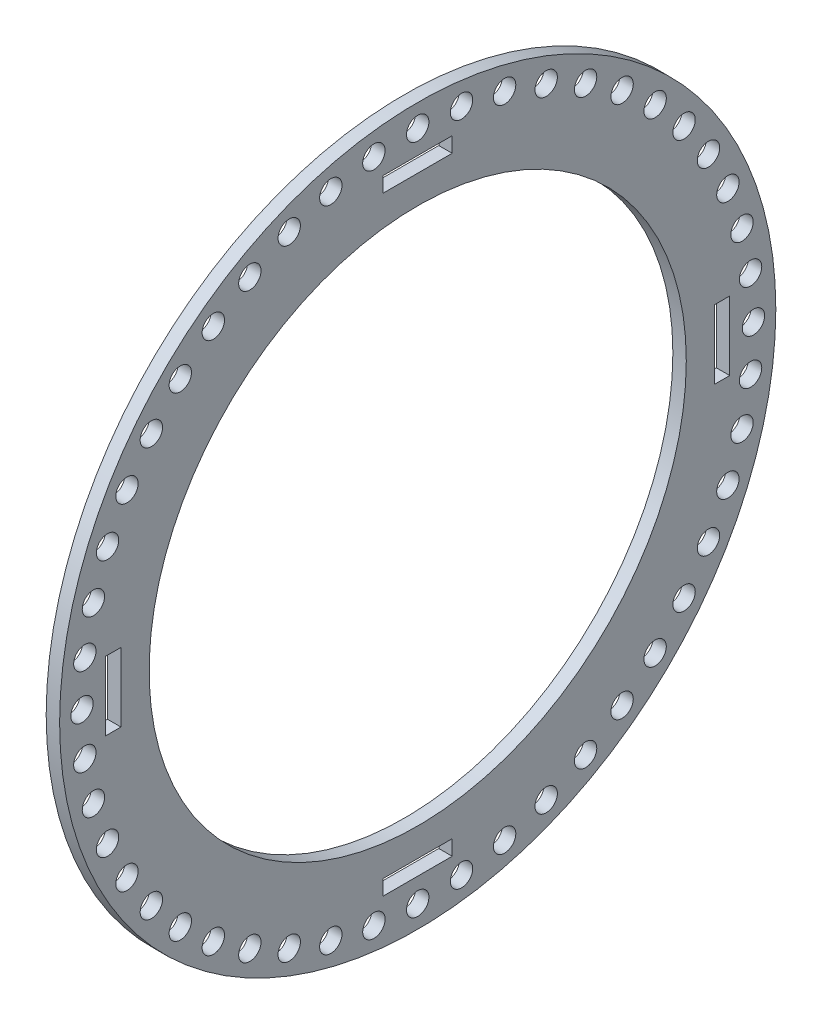
SolidWorks part; units mm, degrees
material "AISI 304"
ref_plane "Front Plane" through (0, 0, 0) normal (0, 0, 1) x (1, 0, 0)
ref_plane "Top Plane" through (0, 0, 0) normal (0, 1, 0) x (1, 0, 0)
ref_plane "Right Plane" through (0, 0, 0) normal (1, 0, 0) x (0, 0, -1)
sketch "Sketch1" plane through (0, 0, 0) normal (1, 0, 0) x (0, 0, -1)
  line L0 (0, 0) -> (0, 40) construction
  line L62 (-3.85, 34.85) -> (3.85, 34.85)
  line L63 (-3.85, 34.85) -> (-3.85, 33.15)
  line L64 (-3.85, 33.15) -> (3.85, 33.15)
  line L65 (3.85, 34.85) -> (3.85, 33.15)
  line L66 (-3.85, 34.85) -> (3.85, 33.15) construction
  line L67 (-3.85, 33.15) -> (3.85, 34.85) construction
  line L103 (34.85, 3.85) -> (34.85, -3.85)
  line L104 (33.15, 3.85) -> (33.15, -3.85)
  line L105 (34.85, 3.85) -> (33.15, 3.85)
  line L106 (34.85, -3.85) -> (33.15, -3.85)
  line L107 (3.85, -34.85) -> (-3.85, -34.85)
  line L108 (3.85, -33.15) -> (-3.85, -33.15)
  line L109 (3.85, -34.85) -> (3.85, -33.15)
  line L110 (-3.85, -34.85) -> (-3.85, -33.15)
  line L111 (-34.85, -3.85) -> (-34.85, 3.85)
  line L112 (-33.15, -3.85) -> (-33.15, 3.85)
  line L113 (-34.85, -3.85) -> (-33.15, -3.85)
  line L114 (-34.85, 3.85) -> (-33.15, 3.85)
  circle A3 centre (0, 0) radius 40
  circle A25 centre (0, 0) radius 30
  point P9 (0, -20)
  point P11 (-20, 0)
  point P22 (0, 34)
  point P29 (20, 0)
  point P31 (0, 30)
  point P75 (0, 0)
  point P81 (0, -1)
  point P93 (0, 0)
  point P95 (0, 0)
  dimension "D2" = 80
  dimension "D3" = 60
  dimension "D7" = 7.7
  dimension "D8" = 1.7
  dimension "D9" = 10
  dimension "D12" = 6
  dimension "D14" = 4
extrude "Boss-Extrude4" add sketch "Sketch1" along normal blind 1.5
sketch "Sketch2" plane through (1.5, 0, 0) normal (1, 0, 0) x (0, 0, -1)
  circle A0 centre (0, 37.5) radius 1.25
  circle A1 centre (0, 0) radius 40 construction
  dimension "D2" = 2.5
  dimension "D1" = 37.5
extrude "Cut-Extrude2" cut sketch "Sketch2" against normal blind 1.5
pattern_circular "CirPattern3" count 48 over 360 about axis through (1.5, 0, 0) along (1, 0, 0) of "Cut-Extrude2"
